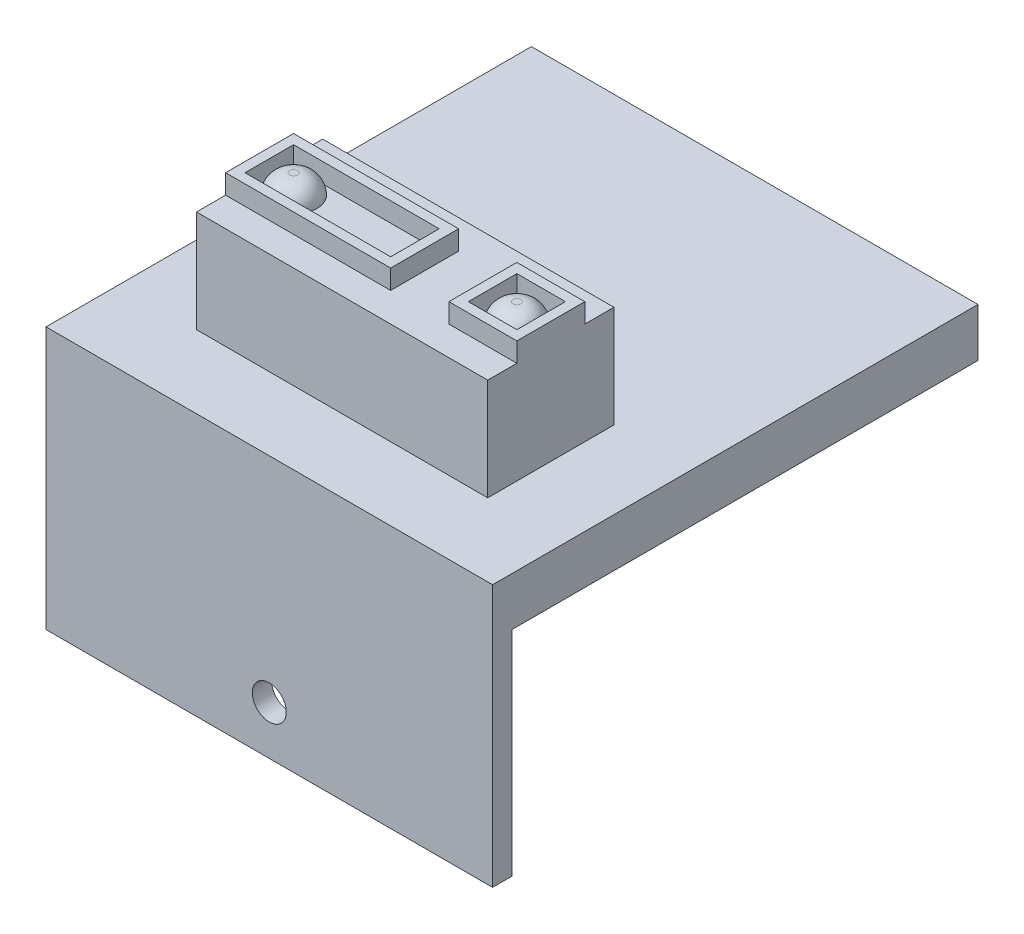
SolidWorks part; units mm, degrees
ref_plane "Front Plane" through (0, 0, 0) normal (0, 0, 1) x (1, 0, 0)
ref_plane "Top Plane" through (0, 0, 0) normal (0, 1, 0) x (1, 0, 0)
ref_plane "Right Plane" through (0, 0, 0) normal (1, 0, 0) x (0, 0, -1)
sketch "Sketch1" plane through (0, 0, 0) normal (0, 1, 0) x (1, 0, 0)
  line L1 (0, 0) -> (46, 0)
  line L2 (0, 0) -> (0, 50)
  line L3 (0, 50) -> (46, 50)
  line L4 (46, 0) -> (46, 50)
  dimension "D1" = 50
  dimension "D2" = 46
extrude "Boss-Extrude1" add sketch "Sketch1" along normal blind 5
sketch "Sketch2" plane through (0, 5, 0) normal (0, 1, 0) x (1, 0, 0)
  line L0 (23, 50) -> (23, 0) construction
  line L1 (8, 7.5) -> (38, 7.5)
  line L2 (8, 7.5) -> (8, 20.5)
  line L3 (8, 20.5) -> (38, 20.5)
  line L4 (38, 7.5) -> (38, 20.5)
  line L5 (46, 50) -> (0, 50) construction
  line L6 (0, 0) -> (46, 0) construction
  dimension "D1" = 13
  dimension "D2" = 30
  dimension "D3" = 7.5
extrude "Boss-Extrude2" add sketch "Sketch2" along normal blind 12.5
sketch "Sketch3" plane through (0, 0, 0) normal (0, -1, 0) x (1, 0, 0)
  line L0 (0, -50) -> (0, 0) construction
  line L1 (46, 0) -> (0, 0)
  line L2 (46, 0) -> (46, -2)
  line L3 (46, -2) -> (0, -2)
  line L4 (0, 0) -> (0, -2)
  dimension "D1" = 2
extrude "Boss-Extrude3" add sketch "Sketch3" along normal blind 22
sketch "Sketch4" plane through (0, 0, -2) normal (0, 0, -1) x (-1, 0, 0)
  line L0 (-23, -22) -> (-23, 0) construction
  line L1 (0, -22) -> (-46, -22) construction
  line L2 (0, 0) -> (-46, 0) construction
  circle A0 centre (-23, -17) radius 1.75
  dimension "D1" = 3.5
  dimension "D2" = 5
extrude "Cut-Extrude1" cut sketch "Sketch4" against normal blind 22
sketch "Sketch5" plane through (0, 17.5, 0) normal (0, 1, 0) x (1, 0, 0)
  line L0 (38, 7.5) -> (38, 20.5) construction
  line L1 (9, 16.5) -> (24, 16.5)
  line L2 (9, 16.5) -> (9, 11.5)
  line L3 (9, 11.5) -> (24, 11.5)
  line L4 (24, 16.5) -> (24, 11.5)
  line L5 (37, 16.5) -> (32, 16.5)
  line L6 (37, 16.5) -> (37, 11.5)
  line L7 (37, 11.5) -> (32, 11.5)
  line L8 (32, 16.5) -> (32, 11.5)
  line L10 (31, 17.5) -> (31, 10.5)
  line L12 (25, 17.5) -> (25, 10.5)
  line L13 (8, 20.5) -> (8, 7.5) construction
  line L14 (31, 17.5) -> (38, 17.5)
  line L15 (8, 20.5) -> (38, 20.5)
  line L16 (8, 20.5) -> (8, 17.5)
  line L17 (8, 17.5) -> (25, 17.5)
  line L18 (38, 20.5) -> (38, 17.5)
  line L19 (8, 7.5) -> (38, 7.5)
  line L20 (8, 7.5) -> (8, 10.5)
  line L21 (8, 10.5) -> (25, 10.5)
  line L22 (38, 7.5) -> (38, 10.5)
  line L23 (31, 10.5) -> (38, 10.5)
  dimension "D1" = 1
  dimension "D2" = 1
  dimension "D3" = 1
  dimension "D4" = 1
  dimension "D5" = 15
  dimension "D6" = 5
  dimension "D7" = 5
  dimension "D8" = 3
  dimension "D9" = 3
  dimension "D10" = 1
extrude "Cut-Extrude2" cut sketch "Sketch5" against normal blind 2
sketch "Sketch6" plane through (0, 15.5, 0) normal (0, 1, 0) x (1, 0, 0)
  line L0 (32, 16.5) -> (37, 11.5) construction
  line L1 (32, 16.5) -> (32, 11.5) construction
  line L2 (37, 16.5) -> (32, 16.5) construction
  line L3 (9, 16.5) -> (14, 11.5) construction
  line L4 (9, 11.5) -> (24, 11.5) construction
  line L6 (9, 16.5) -> (9, 11.5) construction
  circle A0 centre (11.5, 14) radius 2.4
  circle A1 centre (34.5, 14) radius 2.4
  point P11 (13.6192, 14.1148)
  point P17 (11.5092, 14.1148)
  dimension "D1" = 4.8
  dimension "D2" = 4.8
  dimension "D3" = 2.5
extrude "Boss-Extrude6" add sketch "Sketch6" along normal blind 2
fillet "Fillet1" radius 2 2 edges at (34.5, 17.5, -11.6) (11.5, 17.5, -11.6)
